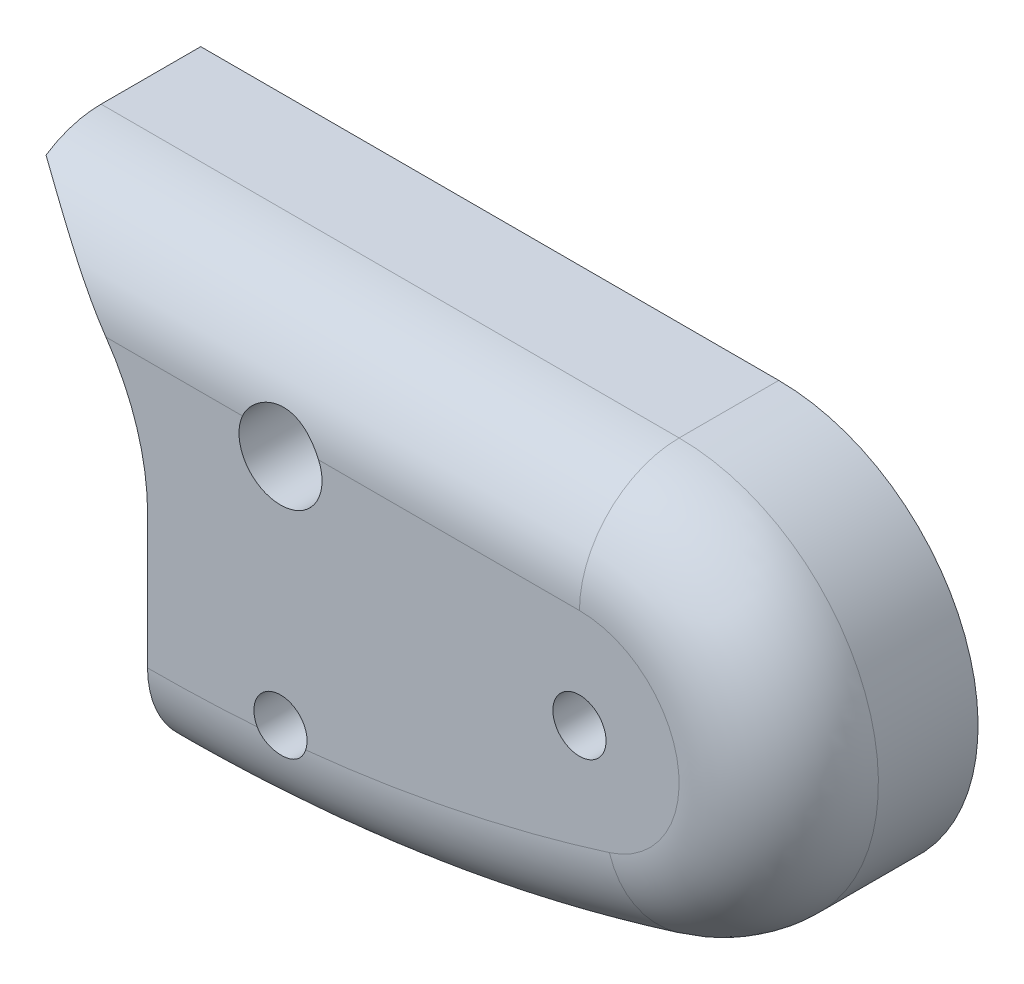
SolidWorks part; units mm, degrees
ref_plane "Front Plane" through (0, 0, 0) normal (0, 0, 1) x (1, 0, 0)
ref_plane "Top Plane" through (0, 0, 0) normal (0, 1, 0) x (1, 0, 0)
ref_plane "Right Plane" through (0, 0, 0) normal (1, 0, 0) x (0, 0, -1)
sketch "Sketch2" plane through (0, 0, 0) normal (0, 0, 1) x (1, 0, 0)
  line L0 (0, 0) -> (0, -7) construction
  line L1 (0, 0) -> (0, 0.9986) construction
  line L2 (0, 0.9986) -> (20.0002, 0.9986) construction
  line L3 (0, 7) -> (20.0002, 6.9986)
  line L5 (7, 0) -> (7, -7)
  line L9 (2.5981, 6.5) -> (2.5981, 7)
  circle A0 centre (0, 0) radius 7
  circle A1 centre (20.0002, 0.9986) radius 6
  spline S0 degree 2 poles (21.8025, -4.7243) (14.5761, -6.9999) (7, -7) knots 0 0 0 1 1 1
extrude "Boss-Extrude1" add sketch "Sketch2" along normal blind 6 contours A1 A0 | A1 | A1 region at (10.9507, 0.354, 0) region at (20.0002, 0.9986, 0)
sketch "Sketch4" plane through (0, 0, 0) normal (0, 0, 1) x (1, 0, 0)
  line L0 (0, 5.2) -> (0, 0)
  line L1 (0, 0) -> (0, -5.2)
  line L2 (0, 5.2) -> (16.2, 5.2)
  line L3 (16.2, 5.2) -> (16.2, -5.2)
  line L4 (16.2, -5.2) -> (0, -5.2)
  line L5 (16.2, 0) -> (18.2, 0) construction
  line L6 (18.2, 0) -> (18.2, 2)
  line L7 (18.2, 2) -> (16.2, 2)
  line L8 (18.2, 0) -> (18.2, -2)
  line L9 (18.2, -2) -> (16.2, -2)
extrude "Middle Insert" cut sketch "Sketch4" along normal blind 2.7 contours L4 L3 L2 L0 L1 | L3 L5 L6 L7 | L5 L3 L9 L8 region at (8.1, 0, 0) region at (17.2, 1, 0) region at (17.2, -1, 0)
sketch "Sketch3" plane through (0, 0, 0) normal (0, 0, 1) x (1, 0, 0)
  line L0 (0, 0) -> (11, 0) construction
  line L1 (20.0002, 0.9986) -> (11, 0.9986) construction
  line L2 (11, 0) -> (11, 3.5) construction
  line L3 (11, 0) -> (11, -3.5) construction
  line L5 (11, 0.9986) -> (11, 0) construction
  circle A0 centre (20.0002, 0.9986) radius 0.8
  circle A1 centre (11, 3.5) radius 0.8
  circle A2 centre (11, -3.5) radius 0.8
extrude "Screw Holes" cut sketch "Sketch3" along normal through all
sketch "Sketch5" plane through (0, 0, 0) normal (0, 0, 1) x (1, 0, 0)
  circle A0 centre (11, 3.5) radius 1.25
extrude "Screw Heads" cut sketch "Sketch5" against normal blind 3 from offset 7
fillet "Fillet2" radius 3 3 edges at (11.2991, 6.9992, 6) (25.9305, 1.9103, 6)
